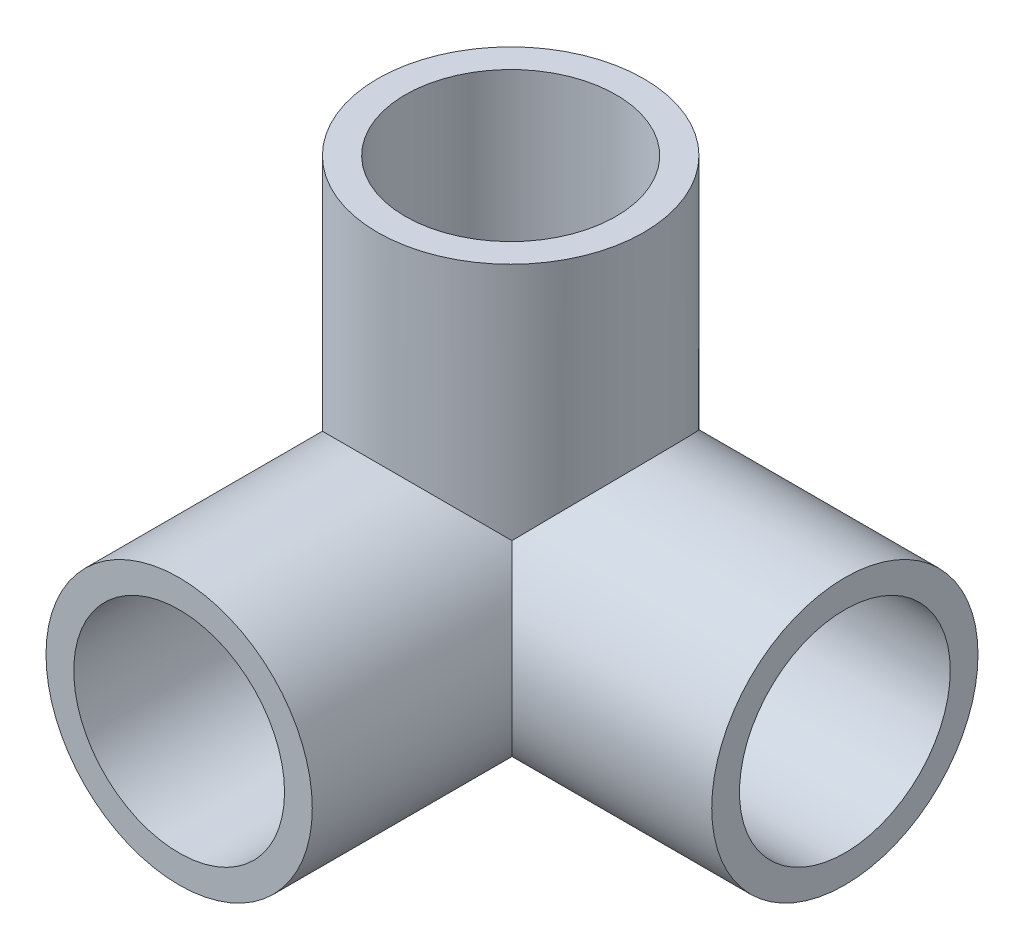
SolidWorks part; units mm, degrees
material "PVC Rigid"
ref_plane "Front Plane" through (0, 0, 0) normal (0, 0, 1) x (1, 0, 0)
ref_plane "Top Plane" through (0, 0, 0) normal (0, 1, 0) x (1, 0, 0)
ref_plane "Right Plane" through (0, 0, 0) normal (1, 0, 0) x (0, 0, -1)
sketch "Sketch2" plane through (0, 0, 0) normal (0, 1, 0) x (1, 0, 0)
  line L0 (0, 0) -> (0, 76.2)
  line L1 (0, 76.2) -> (76.2, 76.2)
  dimension "D1" = 76.2
  dimension "D2" = 76.2
sketch "Sketch3" plane through (0, 0, 0) normal (0, 0, 1) x (1, 0, 0)
  circle A0 centre (0, 0) radius 24.13
  circle A1 centre (0, 0) radius 30.48
  dimension "D1" = 6.35
  dimension "D2" = 48.26
sweep "Sweep1" add profiles "Sketch3" path "Sketch2"
sketch "Sketch4" plane through (0, 0, 0) normal (0, 1, 0) x (1, 0, 0)
  circle A0 centre (0, 75.8983) radius 30.48
  circle A1 centre (0, 75.8983) radius 24.13
  dimension "D1" = 6.35
  dimension "D2" = 48.26
extrude "Boss-Extrude1" add sketch "Sketch4" against normal up to next from offset 76.2
